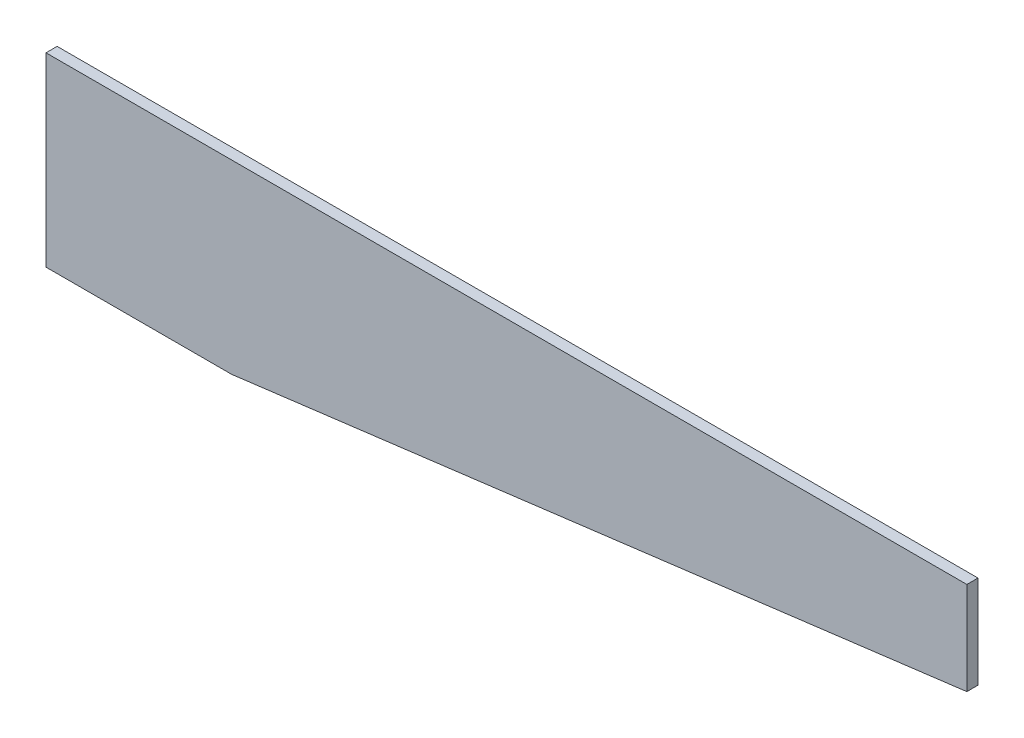
SolidWorks part; units mm, degrees
material "AISI 304"
ref_plane "前视基准面" through (0, 0, 0) normal (0, 0, 1) x (1, 0, 0)
ref_plane "上视基准面" through (0, 0, 0) normal (0, 1, 0) x (1, 0, 0)
ref_plane "右视基准面" through (0, 0, 0) normal (1, 0, 0) x (0, 0, -1)
sketch "草图1" plane through (0, 0, 0) normal (0, 0, 1) x (1, 0, 0)
  line L0 (0, 0) -> (0, 100)
  line L1 (0, 100) -> (496, 100)
  line L2 (496, 100) -> (496, 50)
  line L3 (496, 50) -> (100, 0)
  line L4 (100, 0) -> (0, 0)
  dimension "D1" = 100
  dimension "D2" = 496
  dimension "D3" = 100
  dimension "D4" = 50
base flange "基体-法兰1" sketch "草图1" thickness 6 reverse thickness direction no parameters "D1"=6
sketch "折弯-线1" [suppressed] plane through (0, 0, 0) normal (0, 1, 0) x (1, 0, 0)
sketch "边界框1" [suppressed] plane through (0, 0, 0) normal (0, 1, 0) x (1, 0, 0)
sheet metal parameters "钣金1" thickness 6 parameters "D1"=6
flat pattern "平板型式1" [suppressed]
sketch "折弯-线2" plane through (0, 0, 0) normal (0, 1, 0) x (1, 0, 0)
sketch3d "边界框2" [suppressed]
  line L0 (0, 0, 0) -> (394, 0, 0) construction
  line L1 (0, 100, 0) -> (394, 100, 0) construction
  line L2 (0, 0, 0) -> (0, 100, 0) construction
  line L3 (394, 0, 0) -> (394, 100, 0) construction
